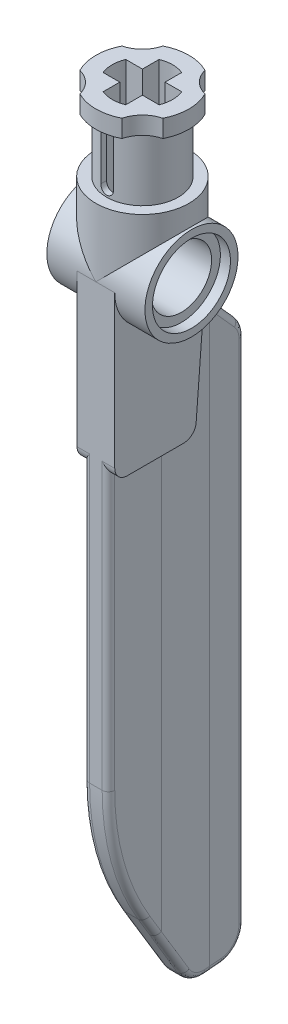
SolidWorks part; units mm, degrees
ref_plane "Front Plane" through (0, 0, 0) normal (0, 0, 1) x (1, 0, 0)
ref_plane "Top Plane" through (0, 0, 0) normal (0, 1, 0) x (1, 0, 0)
ref_plane "Right Plane" through (0, 0, 0) normal (1, 0, 0) x (0, 0, -1)
sketch "Sketch1" plane through (0, 0, 0) normal (0, 1, 0) x (1, 0, 0)
  circle A0 centre (0, 0) radius 2.85
  dimension "D1" = 5.7
extrude "Middle Body" add sketch "Sketch1" along normal mid plane 5.1
sketch "Sketch2" plane through (0, -2.55, 0) normal (0, -1, 0) x (1, 0, 0)
  circle A0 centre (0, 0) radius 3.7
  dimension "D1" = 7.4
extrude "Outer Rim" add sketch "Sketch2" along normal blind 1.4
mirror "Mirror1" about plane through (0, 0, 0) normal (0, 1, 0) of "Outer Rim"
sketch "Sketch3" plane through (0, 0, 0) normal (0, 1, 0) x (1, 0, 0)
  line L1 (2.4, -0.9) -> (-2.4, -0.9)
  line L2 (2.4, -0.9) -> (2.4, 0.9)
  line L3 (2.4, 0.9) -> (-2.4, 0.9)
  line L4 (-2.4, -0.9) -> (-2.4, 0.9)
  line L5 (2.4, -0.9) -> (-2.4, 0.9) construction
  line L6 (2.4, 0.9) -> (-2.4, -0.9) construction
  line L7 (0.9, -2.4) -> (-0.9, -2.4)
  line L8 (0.9, -2.4) -> (0.9, 2.4)
  line L9 (0.9, 2.4) -> (-0.9, 2.4)
  line L10 (-0.9, -2.4) -> (-0.9, 2.4)
  line L11 (0.9, -2.4) -> (-0.9, 2.4) construction
  line L12 (0.9, 2.4) -> (-0.9, -2.4) construction
  circle A0 centre (0, 0) radius 2.4
  dimension "D1" = 4.8
  dimension "D2" = 1.8
extrude "Axle Cut" cut sketch "Sketch3" against normal through all both and the other way through all contours L8 A0 L10 L3 | L3 A0 L1 L10 | L10 L1 L8 L3 | A0 L8 L1 L10 | L1 A0 L3 L8 region at (1.6222, 0, 0) region at (0, 0, 1.6222) region at (0, 0, 0) region at (-1.6222, 0, 0) region at (0, 0, -1.6222)
sketch "Sketch4" plane through (0, 0, 0) normal (0, 0, 1) x (1, 0, 0)
  line L0 (0, -1.9) -> (0, 1.9) construction
  line L1 (-0.5, -1.9) -> (-0.5, 1.9)
  line L2 (0.5, -1.9) -> (0.5, 1.9)
  arc A0 (-0.5, -1.9) -> (0.5, -1.9) centre (0, -1.9) ccw
  arc A1 (0.5, 1.9) -> (-0.5, 1.9) centre (0, 1.9) ccw
  point P2 (0, 0)
  dimension "D2" = 4.8
  dimension "D1" = 1
extrude "Slot Cut" cut sketch "Sketch4" against normal through all both and the other way through all
sketch "Sketch5" plane through (0, 3.95, 0) normal (0, 1, 0) x (1, 0, 0)
  line L0 (0, 0) -> (3.8509, 3.8509) construction
  line L2 (0.9, 0.9) -> (0.9, 2.2249) construction
  circle A0 centre (0, 0) radius 3.2
  circle A3 centre (3.8509, 3.8509) radius 2.246
  circle A4 centre (0, 0) radius 3.7 construction
  circle A5 centre (3.8509, -3.8509) radius 2.246
  circle A6 centre (-3.8509, -3.8509) radius 2.246
  circle A7 centre (-3.8509, 3.8509) radius 2.246
  point P7 (1.6735, 3.2999)
  point P8 (3.2999, 1.6735)
  circle M23 centre (0, 0) radius 3.7
  dimension "D1" = 6.4
  dimension "D3" = 2.3
  dimension "D2" = 45
  dimension "D4" = 4
extrude "Scallop Cut " cut sketch "Sketch5" against normal blind 1.4 contours A7 M23 | L0 A3 M23 | A3 L0 M23 | A5 | A6 region at (2.141, 3.95, -2.7556) region at (2.7556, 3.95, -2.141) region at (-2.4483, 3.95, -2.4483)
sketch "Sketch6" plane through (0, 0, 0) normal (1, 0, 0) x (0, 0, -1)
  line L0 (1.6735, 3.95) -> (-1.6735, 3.95) construction
  circle A0 centre (0, -7.95) radius 3.7
  circle A1 centre (0, -7.95) radius 2.4
  dimension "D1" = 7.4
  dimension "D2" = 4.8
  dimension "D3" = 15.6
extrude "Pin Hole" add sketch "Sketch6" along normal mid plane 7.8 separate body
sketch "Sketch7" plane through (0, -3.95, 0) normal (0, -1, 0) x (1, 0, 0)
  circle A0 centre (0, 0) radius 3.7 construction
  circle A1 centre (0, 0) radius 3.7
extrude "Join " add sketch "Sketch7" along normal up to surface (4 mm away) up to face at (3.9, -7.95, -3.7)
sketch "Sketch8" plane through (3.9, 0, 0) normal (1, 0, 0) x (0, 0, -1)
  circle A2 centre (0, -7.95) radius 3.1
  circle A3 centre (0, -7.95) radius 3.1
  dimension "D1" = 0.7
extrude "Rim Cut " cut sketch "Sketch8" against normal blind 0.8
mirror "Mirror2" about plane through (0, 0, 0) normal (1, 0, 0) of "Rim Cut "
sketch "Sketch9" plane through (0, 0, 0) normal (1, 0, 0) x (0, 0, -1)
  line L0 (-3.7, -7.95) -> (-3.7, -20.05)
  line L1 (-2.7, -21.05) -> (1.7742, -21.05)
  line L2 (2.7712, -20.1269) -> (3.689, -8.2347)
  line L3 (1.6735, 3.95) -> (-1.6735, 3.95) construction
  circle A0 centre (0, -7.95) radius 3.7 construction
  circle A1 centre (0, -7.95) radius 3.7
  arc A2 (1.7742, -21.05) -> (2.7712, -20.1269) centre (1.7742, -20.05) ccw
  arc A3 (-3.7, -20.05) -> (-2.7, -21.05) centre (-2.7, -20.05) ccw
  point P11 (2.7, -21.05)
  point P14 (-3.7, -21.05)
  dimension "D3" = 1
  dimension "D1" = 25
  dimension "D2" = 6.4
extrude "Blade Root" add sketch "Sketch9" along normal mid plane 3 contours L0 A3 L1 A2 L2 A1 region at (0, -15.8147, 0.3138)
sketch "Sketch10" plane through (0, 0, 0) normal (1, 0, 0) x (0, 0, -1)
  line L0 (-3.7, -7.95) -> (-3.7, -48.25)
  line L1 (-3.7, -48.25) -> (2.9, -59.25)
  line L2 (2.9, -59.25) -> (7.5, -59.25)
  line L3 (7.5, -59.25) -> (7.5, -16.15)
  line L4 (7.5, -16.15) -> (3.4255, -11.65)
  line L5 (2.7712, -20.1269) -> (3.689, -8.2347) construction
  line L6 (3.4255, -11.65) -> (3.689, -8.2347)
  line L7 (1.6735, 3.95) -> (-1.6735, 3.95) construction
  arc A0 (-3.7, -7.95) -> (3.689, -8.2347) centre (0, -7.95) ccw construction
  arc A1 (-3.7, -7.95) -> (3.689, -8.2347) centre (0, -7.95) ccw
  dimension "D1" = 63.2
  dimension "D2" = 4.6
  dimension "D3" = 11
  dimension "D4" = 15.6
  dimension "D5" = 4.5
  dimension "D6" = 11.2
extrude "Blade" add sketch "Sketch10" along normal mid plane 2
chamfer "Chamfer1" distance 0.4 distance2 5 2 edges at (-1, -37.7, -7.5) (1, -37.7, -7.5) first distance on face at (0, -37.7, -7.5)
fillet "Fillet1" radius 50 2 edges at (-1, -39.6606, -2.5) (1, -39.6606, -2.5)
fillet "Fillet2" radius 2 3 edges at (0, -59.25, -2.9) (0, -59.25, -7.5) (0, -16.15, -7.5)
fillet "Fillet3" radius 20 1 edges at (0, -48.25, 3.7)
fillet "Fillet4" radius 0.5 24 edges at (-1, -31.3802, 3.7) (-1, -48.049, 2.9743) (-1, -54.1278, 0.1733) (-0.8805, -12.2383, -3.9581) (-0.7411, -14.2024, -5.7365) (-0.6107, -16.2016, -7.3662) (-0.6, -37.0855, -7.5) (-0.6469, -58.6642, -6.9142) (-0.8004, -59.25, -4.9952) (-0.8586, -59.25, -4.2615) (-0.9177, -59.1372, -3.3703) (1, -31.3802, 3.7) (0.8805, -12.2383, -3.9581) (0.7411, -14.2024, -5.7365) (0.6107, -16.2016, -7.3662) (0.6, -37.0855, -7.5) (0.6469, -58.6642, -6.9142) (0.8004, -59.25, -4.9952) (0.8586, -59.25, -4.2615) (0.9493, -58.7884, -2.7544) (0.9918, -56.7674, -1.4104) (1, -54.1278, 0.1733) (-0.9918, -56.7674, -1.4104) (1, -48.049, 2.9743)
